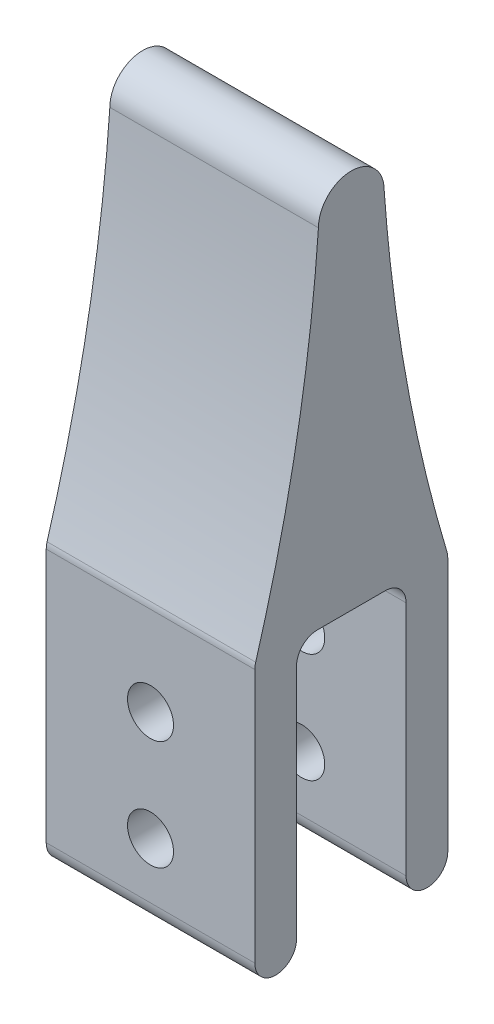
SolidWorks part; units mm, degrees
ref_plane "Front Plane" through (0, 0, 0) normal (0, 0, 1) x (1, 0, 0)
ref_plane "Top Plane" through (0, 0, 0) normal (0, 1, 0) x (1, 0, 0)
ref_plane "Right Plane" through (0, 0, 0) normal (1, 0, 0) x (0, 0, -1)
sketch "Sketch1" plane through (0, 0, 0) normal (1, 0, 0) x (0, 0, -1)
  line L0 (-5, 0) -> (-8.81, 0)
  line L1 (-8.81, 0) -> (-8.81, 25.4)
  line L2 (0, -1000) -> (0, 49000) construction
  line L3 (-8.81, 25.4) -> (8.81, 25.4) construction
  line L4 (-5, 0) -> (-5, 25.4)
  line L5 (-5, 25.4) -> (5, 25.4)
  line L6 (5, 0) -> (5, 25.4)
  line L7 (8.81, 0) -> (8.81, 25.4)
  line L8 (5, 0) -> (8.81, 0)
  arc A0 (3, 57.15) -> (-3, 57.15) centre (0, 57.15) ccw
  spline S0 degree 2 poles (-8.81, 25.4) (-4.1642, 40.9193) (-3, 57.15) knots 0 0 0 1 1 1
  spline S1 degree 2 poles (8.81, 25.4) (4.1642, 40.9193) (3, 57.15) knots 0 0 0 1 1 1
  point P10 (0, 25.4)
  point P12 (0, 25.4)
  point P14 (-6.2407, 35.1942)
  dimension "D5" = 6
  dimension "D1" = 5
  dimension "D2" = 3.81
  dimension "D3" = 25.4
  dimension "D4" = 31.75
  dimension "D6" = 25.4
extrude "Boss-Extrude1" add sketch "Sketch1" along normal blind 19.05
sketch "Sketch2" plane through (0, 0, -8.81) normal (0, 0, -1) x (-1, 0, 0)
  line L0 (-9.525, -974.6) -> (-9.525, 49025.4) construction
  line L1 (-19.05, 25.4) -> (0, 25.4) construction
  line L2 (-19.05, 0) -> (0, 0) construction
  circle A0 centre (-9.525, 7) radius 2.1
  circle A1 centre (-9.525, 17) radius 2.1
  point P5 (-9.525, 25.4)
  point P9 (-9.525, 14.201)
  dimension "D2" = 4.2
  dimension "D3" = 4.2
  dimension "D1" = 10
  dimension "D4" = 7
extrude "Cut-Extrude1" cut sketch "Sketch2" against normal through all
fillet "Fillet2" radius 1.905 8 edges at (9.525, 25.4, -8.81) (9.525, 0, -8.81) (9.525, 0, -5) (9.525, 0, 5) (9.525, 0, 8.81) (9.525, 25.4, -5) (9.525, 25.4, 5) (9.525, 25.4, 8.81)
